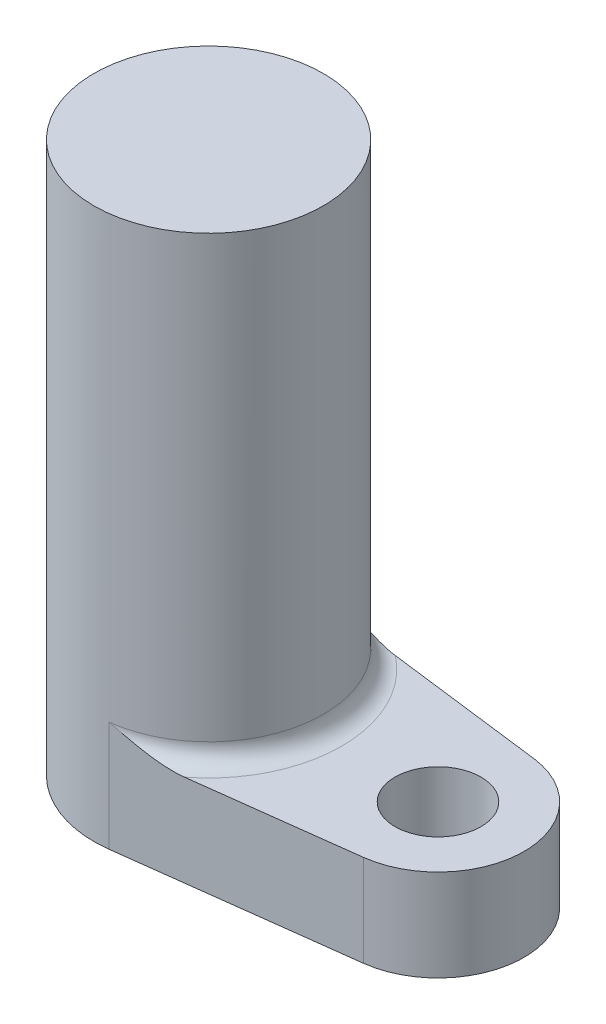
SolidWorks part; units mm, degrees
ref_plane "Front Plane" through (0, 0, 0) normal (0, 0, 1) x (1, 0, 0)
ref_plane "Top Plane" through (0, 0, 0) normal (0, 1, 0) x (1, 0, 0)
ref_plane "Right Plane" through (0, 0, 0) normal (1, 0, 0) x (0, 0, -1)
sketch "Sketch1" plane through (0, 0, 0) normal (0, 1, 0) x (1, 0, 0)
  circle A0 centre (0, 0) radius 3.175
  dimension "D1" = 6.35
extrude "Boss-Extrude1" add sketch "Sketch1" along normal blind 12.7
cosmetic thread "Cosmetic Thread1" parameters "D1"=7.9375, "D2"=5.268
sketch "Sketch2" plane through (0, 0, 0) normal (0, -1, 0) x (1, 0, 0)
  line L0 (-10.6761, 0) -> (14.4716, 0) construction
  line L1 (0.3969, 3.1501) -> (6.6477, 2.3626)
  line L2 (6.6477, -2.3626) -> (0.3969, -3.1501)
  circle A0 centre (6.35, 0) radius 1.1906
  circle A1 centre (0, 0) radius 3.175 construction
  arc A2 (6.6477, 2.3626) -> (6.6477, -2.3626) centre (6.35, 0) cw
  circle M4 centre (0, 0) radius 3.175
  dimension "D2" = 2.3813
  dimension "D3" = 2.3813
  dimension "D1" = 6.35
extrude "Boss-Extrude2" add sketch "Sketch2" along normal blind 2.54 contours L0 M4 | L0 A0 A2 L1 M4 | L0 L2 A2 A0 M4 | L0 M4 region at (0, 0, 1.3475) region at (0, 0, -1.3475) region at (5.108, 0, 1.4695) region at (5.108, 0, -1.4695)
fillet "Fillet1" radius 0.508 1 edges at (3.175, 0, 0)
sketch "Sketch3" plane through (0, 0, 0) normal (0, 1, 0) x (1, 0, 0)
  line L0 (0, -5.1656) -> (0, 6.1347) construction
  line L1 (-6.2309, 0) -> (11.0317, 0) construction
  line L3 (-1.1906, -4.3637) -> (1.1906, -4.3637)
  line L4 (-1.1906, -4.3637) -> (-1.1906, -1.9863)
  line L5 (-1.1906, -1.9863) -> (1.1906, -1.9863)
  line L6 (1.1906, -4.3637) -> (1.1906, -1.9863)
  line L7 (-1.1906, -4.3637) -> (1.1906, -1.9863) construction
  line L8 (-1.1906, -1.9863) -> (1.1906, -4.3637) construction
  arc A0 (0.3969, 3.1501) -> (0.3969, -3.1501) centre (0, 0) ccw construction
  point P5 (0, -3.175)
  dimension "D1" = 1.1887
  dimension "D2" = 2.3813
equation "\"0.3n\"=0.4"
